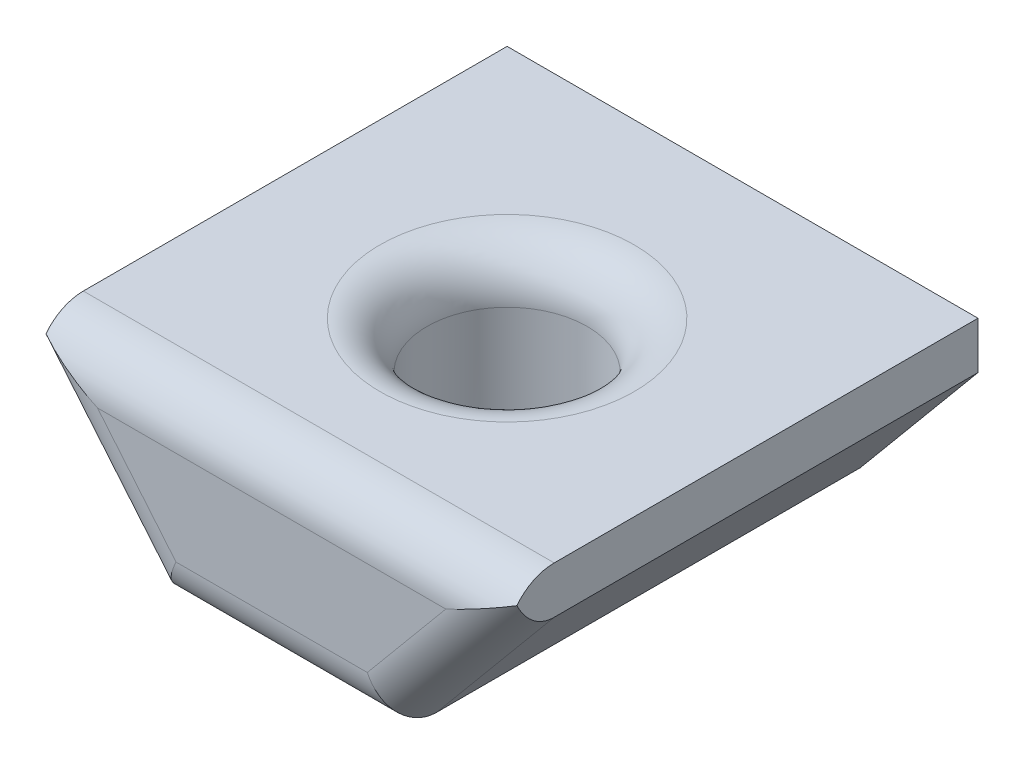
SolidWorks part; units mm, degrees
ref_plane "Front Plane" through (0, 0, 0) normal (0, 0, 1) x (1, 0, 0)
ref_plane "Top Plane" through (0, 0, 0) normal (0, 1, 0) x (1, 0, 0)
ref_plane "Right Plane" through (0, 0, 0) normal (1, 0, 0) x (0, 0, -1)
sketch "Sketch1" plane through (0, 0, 0) normal (0, 0, 1) x (1, 0, 0)
  line L0 (0, 0) -> (0, -18145.3617) construction
  line L1 (-2.5, 0) -> (2.5, 0)
  line L2 (2.5, 0) -> (5, 3)
  line L3 (5, 3) -> (5, 4)
  line L4 (5, 4) -> (-5, 4)
  line L5 (-5, 3) -> (-5, 4)
  line L6 (-2.5, 0) -> (-5, 3)
  point P9 (0, 4)
  point P11 (0, 0)
  dimension "D1" = 2.5
  dimension "D2" = 5
  dimension "D3" = 3
  dimension "D4" = 1
extrude "Boss-Extrude1" add sketch "Sketch1" along normal blind 10
sketch "Sketch3" plane through (0, 4, 0) normal (0, 1, 0) x (1, 0, 0)
  line L1 (5, -10) -> (5, 0) construction
  circle A0 centre (0, -5) radius 1.7
  point P5 (5, -5)
  dimension "D1" = 3.4
extrude "Cut-Extrude1" cut sketch "Sketch3" against normal through all
fillet "Fillet2" radius 1 5 edges at (0, 0, 10) (3.75, 1.5, 10) (-3.75, 1.5, 10) (0, 4, 10) (0, 4, 6.7)
